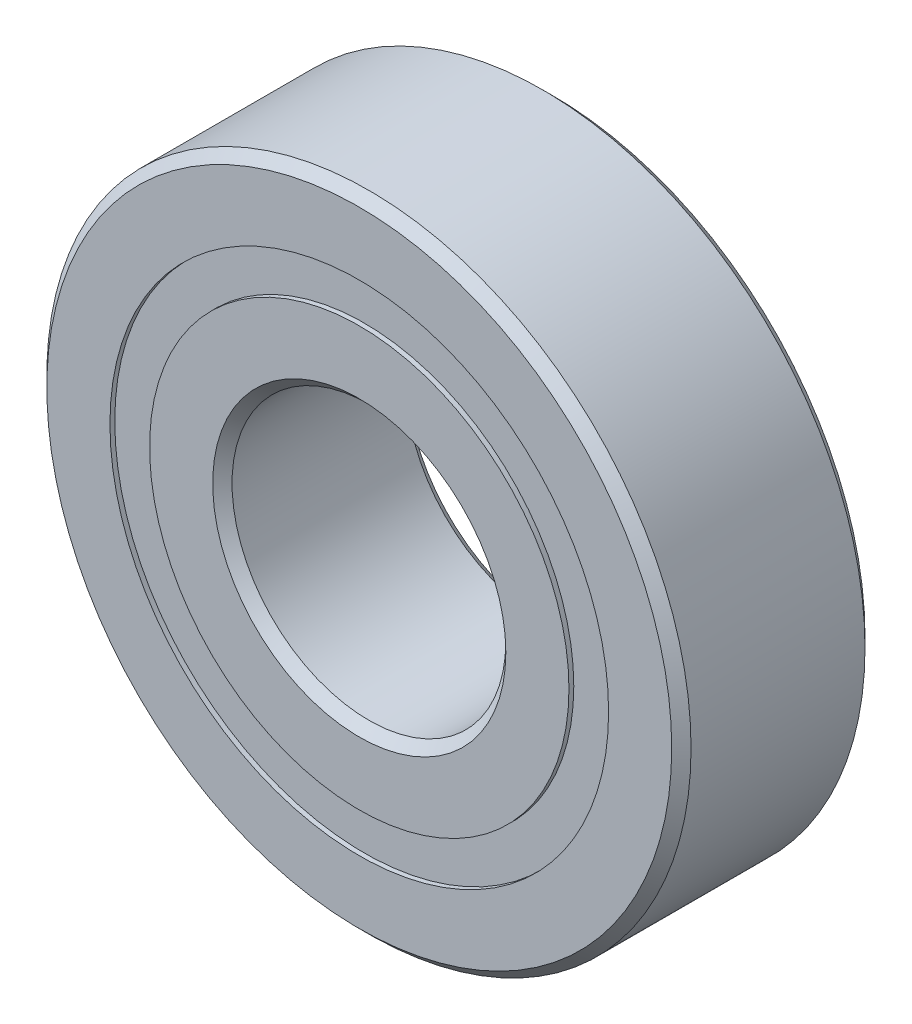
SolidWorks part; units mm, degrees
ref_plane "Front Plane" through (0, 0, 0) normal (0, 0, 1) x (1, 0, 0)
ref_plane "Top Plane" through (0, 0, 0) normal (0, 1, 0) x (1, 0, 0)
ref_plane "Right Plane" through (0, 0, 0) normal (1, 0, 0) x (0, 0, -1)
sketch "Sketch1" plane through (0, 0, 0) normal (1, 0, 0) x (0, 0, -1)
  line L0 (-6, 0) -> (6, 0) construction
  line L1 (0, 20) -> (0, -20) construction
  line L2 (5.4, 20) -> (-5.4, 20)
  line L3 (-5.4, 20) -> (-6, 19.4)
  line L4 (-6, 19.4) -> (-6, 15.4808)
  line L5 (-6, 15.4808) -> (-2.6667, 15.4808)
  line L6 (6, 15.4808) -> (2.6667, 15.4808)
  line L7 (6, 19.4) -> (6, 15.4808)
  line L8 (5.4, 20) -> (6, 19.4)
  line L9 (0, 20) -> (0, 14.25) construction
  line L10 (0, 14.25) -> (0, 8.5) construction
  arc A0 (-2.6667, 15.4808) -> (2.6667, 15.4808) centre (0, 14.25) cw
  point P14 (0, 8.5)
  dimension "Width" = 12
  dimension "OD" = 40
  dimension "D1" = 45
  dimension "D2" = 0.6
  dimension "Shaft Dia" = 17
  dimension "D3" = 5.3333
  dimension "D4" = 1.2308
revolve "Revolve1" add sketch "Sketch1" angle 360 about L0
sketch "Sketch3" plane through (0, 0, 0) normal (1, 0, 0) x (0, 0, -1)
  line L0 (-6, 13.0192) -> (-2.6667, 13.0192)
  line L1 (0, 20) -> (0, -20) construction
  line L2 (-6, 19.4) -> (-6, 15.4808) construction
  line L3 (-6, 13.0192) -> (-6, 9.1)
  line L4 (-5.4, 20) -> (-6, 19.4) construction
  line L5 (-6, 9.1) -> (-5.4, 8.5)
  line L6 (-5.4, 8.5) -> (5.4, 8.5)
  line L7 (5.4, 20) -> (5.4, -20) construction
  line L8 (5.4, 8.5) -> (6, 9.1)
  line L9 (6, -19.4) -> (6, 19.4) construction
  line L10 (6, 9.1) -> (6, 13.0192)
  line L11 (6, 13.0192) -> (2.6667, 13.0192)
  line L13 (5.4, 20) -> (6, 19.4) construction
  arc A0 (2.6667, 15.4808) -> (-2.6667, 15.4808) centre (0, 14.25) ccw construction
  arc A1 (2.6667, 13.0192) -> (-2.6667, 13.0192) centre (0, 14.25) cw
revolve "Revolve3" add sketch "Sketch3" angle 360 about L0
sketch "Sketch4" plane through (0, 0, 0) normal (1, 0, 0) x (0, 0, -1)
  line L0 (-2.937, 14.25) -> (2.937, 14.25)
  arc A2 (-2.937, 14.25) -> (2.937, 14.25) centre (0, 14.25) cw
  arc A3 (2.6667, 15.4808) -> (-2.6667, 15.4808) centre (0, 14.25) ccw construction
revolve "Revolve4" add sketch "Sketch4" angle 360 about L0
ref_axis "Axis1" through (0, 0, -6) along (0, 0, 1)
pattern_circular "CirPattern1" count 14 every 25.714 about axis through (0, 0, -6) along (0, 0, 1) of bodies 104
sketch "Sketch6" plane through (0, 0, 0) normal (1, 0, 0) x (0, 0, -1)
  line L0 (-6, 15.4808) -> (-2.6667, 15.4808) construction
  line L1 (-5.7, 15.4808) -> (-2.937, 15.4808)
  line L2 (-5.7, 15.4808) -> (-5.7, 13.0192)
  line L3 (-5.7, 13.0192) -> (-2.937, 13.0192)
  line L4 (-2.937, 15.4808) -> (-2.937, 13.0192)
  line L5 (-6, 13.0192) -> (-2.6667, 13.0192) construction
  line L6 (6, 15.4808) -> (2.6667, 15.4808) construction
  line L7 (5.7, 15.4808) -> (2.937, 15.4808)
  line L8 (5.7, 15.4808) -> (5.7, 13.0192)
  line L9 (5.7, 13.0192) -> (2.937, 13.0192)
  line L10 (2.937, 15.4808) -> (2.937, 13.0192)
  line L11 (6, 13.0192) -> (2.6667, 13.0192) construction
  line L12 (-5.4, 20) -> (-6, 19.4) construction
  point P18 (-5.7, 19.7)
revolve "Revolve5" add sketch "Sketch6" angle 360 about L0
equation "\"D2@Sketch1\" = \"Width@Sketch1\"*.05"
equation "\"D3@Sketch1\" = \"Width@Sketch1\"/2.25"
equation "\"D4@Sketch1\" = (((\"OD@Sketch1\"-\"Width@Sketch1\")/2)/3.25)/3.5"
equation "\"D2@CirPattern1\" = 360/\"Balls@CirPattern1\""
